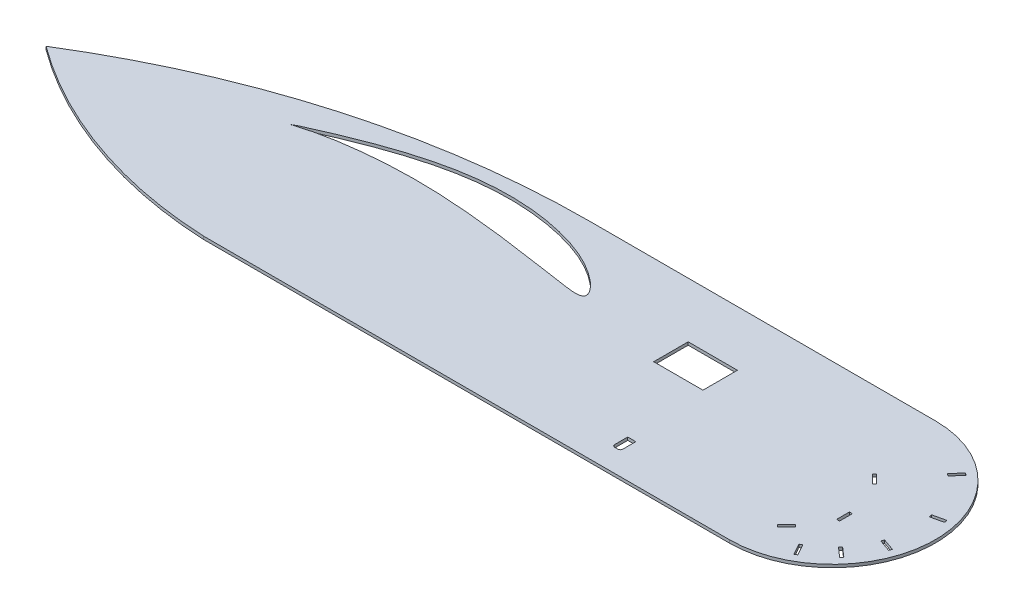
SolidWorks part; units mm, degrees
ref_plane "Front Plane" through (0, 0, 0) normal (0, 0, 1) x (1, 0, 0)
ref_plane "Top Plane" through (0, 0, 0) normal (0, 1, 0) x (1, 0, 0)
ref_plane "Right Plane" through (0, 0, 0) normal (1, 0, 0) x (0, 0, -1)
sketch "Sketch1" plane through (0, 0, 0) normal (0, 1, 0) x (1, 0, 0)
  line L0 (800, 104.5) -> (0, 104.5) construction
  line L1 (266.4083, 0) -> (800, 0)
  line L2 (0, 0) -> (0, 209) construction
  line L3 (449.0139, 209) -> (800, 209)
  line L7 (247.07, 156) -> (658.07, 156) construction
  arc A0 (800, 209) -> (800, 0) centre (800, 104.5) cw
  arc A2 (266.4083, 0) -> (19.4291, 86.8932) centre (286.1808, 450.645) cw
  arc A4 (19.4291, 86.8932) -> (449.0139, 209) centre (449.0139, -607.7159) cw
  point P1 (800, 202.4986)
  dimension "D1" = 800
  dimension "D2" = 53
extrude "Boss-Extrude1" add sketch "Sketch1" along normal blind 3
sketch "Sketch2" plane through (0, 0, 0) normal (0, -1, 0) x (1, 0, 0)
  line L0 (605.07, -153) -> (605.07, 81) construction
  line L1 (655.07, -153) -> (605.07, -153)
  line L2 (655.07, -153) -> (655.07, -118)
  line L3 (655.07, -118) -> (605.07, -118)
  line L4 (823.6893, -121.2328) -> (814.4969, -130.4252)
  line L5 (814.4969, -130.4252) -> (816.6182, -132.5465)
  line L6 (816.6182, -132.5465) -> (825.8106, -123.3541)
  line L7 (825.8106, -123.3541) -> (823.6893, -121.2328)
  line L8 (823.6893, -121.2328) -> (814.4969, -130.4252)
  line L9 (814.4969, -130.4252) -> (816.6182, -132.5465)
  line L10 (816.6182, -132.5465) -> (825.8106, -123.3541)
  line L11 (825.8106, -123.3541) -> (823.6893, -121.2328)
  line L12 (605.07, -153) -> (605.07, -118)
  line L20 (841.7076, -32.7369) -> (848.0358, -21.3811)
  line L21 (848.0358, -21.3811) -> (845.4152, -19.9208)
  line L22 (845.4152, -19.9208) -> (839.0871, -31.2766)
  line L23 (839.0871, -31.2766) -> (841.7076, -32.7369)
  line L24 (841.7076, -32.7369) -> (848.0358, -21.3811)
  line L25 (848.0358, -21.3811) -> (845.4152, -19.9208)
  line L26 (845.4152, -19.9208) -> (839.0871, -31.2766)
  line L27 (839.0871, -31.2766) -> (841.7076, -32.7369)
  line L28 (839.4566, -85.3169) -> (839.4566, -72.3169)
  line L29 (839.4566, -72.3169) -> (836.4566, -72.3169)
  line L30 (836.4566, -72.3169) -> (836.4566, -85.3169)
  line L31 (836.4566, -85.3169) -> (839.4566, -85.3169)
  line L32 (839.4566, -85.3169) -> (839.4566, -72.3169)
  line L33 (839.4566, -72.3169) -> (836.4566, -72.3169)
  line L34 (836.4566, -72.3169) -> (836.4566, -85.3169)
  line L35 (836.4566, -85.3169) -> (839.4566, -85.3169)
  line L37 (212.57, -142.2618) -> (212.57, -142.2948)
  line L38 (212.57, -142.2618) -> (212.57, -142.2948)
  line L40 (658.07, -25.4734) -> (658.07, -38.6734)
  line L41 (663.77, -22.9734) -> (660.57, -22.9734)
  line L42 (666.27, -38.6734) -> (666.27, -25.4734)
  line L43 (658.07, -38.6734) -> (666.27, -38.6734)
  line L44 (658.07, -25.4734) -> (658.07, -38.6734)
  line L45 (663.77, -22.9734) -> (660.57, -22.9734)
  line L46 (666.27, -38.6734) -> (666.27, -25.4734)
  line L47 (658.07, -38.6734) -> (666.27, -38.6734)
  line L188 (852.6149, -168.6961) -> (861.0358, -178.6) construction
  line L189 (861.0358, -178.6) -> (863.3214, -176.6567) construction
  line L190 (863.3214, -176.6567) -> (854.9004, -166.7528) construction
  line L191 (854.9004, -166.7528) -> (852.6149, -168.6961) construction
  line L192 (880.5688, -124.4531) -> (893.242, -127.3497) construction
  line L193 (893.242, -127.3497) -> (893.9105, -124.4251) construction
  line L194 (893.9105, -124.4251) -> (881.2373, -121.5286) construction
  line L195 (881.2373, -121.5286) -> (880.5688, -124.4531) construction
  line L196 (878.8444, -78.5572) -> (891.1176, -74.2715) construction
  line L197 (891.1176, -74.2715) -> (890.1286, -71.4393) construction
  line L198 (890.1286, -71.4393) -> (877.8554, -75.7249) construction
  line L199 (877.8554, -75.7249) -> (878.8444, -78.5572) construction
  line L200 (863.6104, -51.1786) -> (873.4206, -42.6486) construction
  line L201 (873.4206, -42.6486) -> (871.4522, -40.3847) construction
  line L202 (871.4522, -40.3847) -> (861.642, -48.9147) construction
  line L203 (861.642, -48.9147) -> (863.6104, -51.1786) construction
  line L204 (822.4089, -44.7346) -> (813.2165, -35.5422) construction
  line L205 (813.2165, -35.5422) -> (811.0952, -37.6635) construction
  line L206 (811.0952, -37.6635) -> (820.2876, -46.8559) construction
  line L207 (820.2876, -46.8559) -> (822.4089, -44.7346) construction
  line L208 (852.6149, -168.6961) -> (861.0358, -178.6)
  line L209 (861.0358, -178.6) -> (863.3214, -176.6567)
  line L210 (863.3214, -176.6567) -> (854.9004, -166.7528)
  line L211 (854.9004, -166.7528) -> (852.6149, -168.6961)
  line L212 (880.5688, -124.4531) -> (893.242, -127.3497)
  line L213 (893.242, -127.3497) -> (893.9105, -124.4251)
  line L214 (893.9105, -124.4251) -> (881.2373, -121.5286)
  line L215 (881.2373, -121.5286) -> (880.5688, -124.4531)
  line L216 (878.8444, -78.5572) -> (891.1176, -74.2715)
  line L217 (891.1176, -74.2715) -> (890.1286, -71.4393)
  line L218 (890.1286, -71.4393) -> (877.8554, -75.7249)
  line L219 (877.8554, -75.7249) -> (878.8444, -78.5572)
  line L220 (863.6104, -51.1786) -> (873.4206, -42.6486)
  line L221 (873.4206, -42.6486) -> (871.4522, -40.3847)
  line L222 (871.4522, -40.3847) -> (861.642, -48.9147)
  line L223 (861.642, -48.9147) -> (863.6104, -51.1786)
  line L224 (822.4089, -44.7346) -> (813.2165, -35.5422)
  line L225 (813.2165, -35.5422) -> (811.0952, -37.6635)
  line L226 (811.0952, -37.6635) -> (820.2876, -46.8559)
  line L227 (820.2876, -46.8559) -> (822.4089, -44.7346)
  arc A2 (660.57, -22.9734) -> (658.07, -25.4734) centre (660.57, -25.4734) ccw
  arc A3 (666.27, -25.4734) -> (663.77, -22.9734) centre (663.77, -25.4734) ccw
  arc A4 (660.57, -22.9734) -> (658.07, -25.4734) centre (660.57, -25.4734) ccw
  arc A5 (666.27, -25.4734) -> (663.77, -22.9734) centre (663.77, -25.4734) ccw
  spline S1 degree 3 poles (-935.9633, -1778.8288) (190.5889, -95.3438) (194.6064, -131.763) (215.6642, -144.2206) (218.7234, -145.7779) (222.7838, -147.5804) (227.7591, -149.7808) (233.6732, -152.3729) (243.3346, -156.474) (254.0716, -160.9286) (265.8113, -165.5514) (275.5598, -169.1926) (285.8203, -172.7897) (300.2132, -177.4429) (315.0475, -181.6144) (330.2168, -185.0782) (341.7168, -187.2628) (353.2384, -188.9705) (364.7498, -190.1898) (376.2222, -190.8893) (387.6115, -191.0869) (398.8538, -190.7647) (413.4214, -189.6963) (427.5808, -187.7) (441.1954, -184.8275) (450.8219, -182.3197) (459.9489, -179.4697) (468.5117, -176.2876) (476.4536, -172.8247) (483.7151, -169.1289) (490.2481, -165.2848) (496.0197, -161.4069) (500.998, -157.5857) (505.1476, -153.8841) (508.4473, -150.3827) (510.8522, -147.1808) (512.2305, -144.519) (512.6724, -142.438) (512.366, -140.694) (510.8363, -139.2679) (508.3008, -138.6046) (504.9907, -138.3969) (500.8451, -138.6329) (495.8864, -139.207) (490.1274, -140.0338) (483.6007, -141.0142) (476.346, -142.082) (468.4189, -143.2709) (459.8696, -144.553) (447.4042, -146.414) (434.3028, -148.292) (413.2306, -151.0803) (394.9165, -153.1705) (372.4131, -155.1852) (353.2786, -156.4974) (334.1039, -157.1205) (318.8375, -157.1193) (307.5693, -156.8631) (296.5448, -156.3424) (285.8536, -155.5986) (275.5863, -154.6546) (265.8296, -153.5569) (256.6735, -152.3128) (248.205, -150.9585) (240.5101, -149.5233) (233.6661, -148.0641) (227.7356, -146.6296) (222.7715, -145.2056) (218.7746, -143.9126) (215.7248, -142.9952) (193.3721, -137.343) (166.6151, -157.487) (567.9657, 1824.9991) knots -0.10608 -0.10608 -0.10608 -0.10608 0.001413 0.005226 0.010781 0.017816 0.026461 0.036791 0.048686 0.076639 0.092363 0.109003 0.126387 0.144339 0.181313 0.200023 0.218713 0.237261 0.255692 0.274037 0.292193 0.310133 0.327788 0.362002 0.378421 0.394287 0.409543 0.424114 0.437938 0.450942 0.463044 0.474154 0.484165 0.493024 0.500713 0.507126 0.51213 0.514904 0.517171 0.520262 0.524245 0.529498 0.536092 0.544061 0.553363 0.563905 0.575615 0.58842 0.602227 0.616944 0.648676 0.665501 0.718564 0.736789 0.773513 0.810245 0.828489 0.846493 0.864125 0.881249 0.897725 0.913415 0.928184 0.941897 0.954411 0.965603 0.97535 0.983576 0.990285 0.995433 0.9988 1.100441 1.100441 1.100441 1.100441 only from (212.57, -142.2948) to (212.57, -142.2618)
  spline S2 degree 3 poles (212.57, -142.2948) (212.8151, -142.4601) (213.7215, -143.0713) (215.6642, -144.2206) (218.7234, -145.7779) (222.7838, -147.5804) (227.7591, -149.7808) (233.6732, -152.3729) (243.3346, -156.474) (254.0716, -160.9286) (265.8113, -165.5514) (275.5598, -169.1926) (285.8203, -172.7897) (300.2132, -177.4429) (315.0475, -181.6144) (330.2168, -185.0782) (341.7168, -187.2628) (353.2384, -188.9705) (364.7498, -190.1898) (376.2222, -190.8893) (387.6115, -191.0869) (398.8538, -190.7647) (413.4214, -189.6963) (427.5808, -187.7) (441.1954, -184.8275) (450.8219, -182.3197) (459.9489, -179.4697) (468.5117, -176.2876) (476.4536, -172.8247) (483.7151, -169.1289) (490.2481, -165.2848) (496.0197, -161.4069) (500.998, -157.5857) (505.1476, -153.8841) (508.4473, -150.3827) (510.8522, -147.1808) (512.2305, -144.519) (512.6724, -142.438) (512.366, -140.694) (510.8363, -139.2679) (508.3008, -138.6046) (504.9907, -138.3969) (500.8451, -138.6329) (495.8864, -139.207) (490.1274, -140.0338) (483.6007, -141.0142) (476.346, -142.082) (468.4189, -143.2709) (459.8696, -144.553) (447.4042, -146.414) (434.3028, -148.292) (413.2306, -151.0803) (394.9165, -153.1705) (372.4131, -155.1852) (353.2786, -156.4974) (334.1039, -157.1205) (318.8375, -157.1193) (307.5693, -156.8631) (296.5448, -156.3424) (285.8536, -155.5986) (275.5863, -154.6546) (265.8296, -153.5569) (256.6735, -152.3128) (248.205, -150.9585) (240.5101, -149.5233) (233.6661, -148.0641) (227.7356, -146.6296) (222.7715, -145.2056) (218.7746, -143.9126) (215.7248, -142.9952) (213.7534, -142.4967) (212.8162, -142.3107) (212.57, -142.2618) knots 0 0 0 0 0.001413 0.005226 0.010781 0.017816 0.026461 0.036791 0.048686 0.076639 0.092363 0.109003 0.126387 0.144339 0.181313 0.200023 0.218713 0.237261 0.255692 0.274037 0.292193 0.310133 0.327788 0.362002 0.378421 0.394287 0.409543 0.424114 0.437938 0.450942 0.463044 0.474154 0.484165 0.493024 0.500713 0.507126 0.51213 0.514904 0.517171 0.520262 0.524245 0.529498 0.536092 0.544061 0.553363 0.563905 0.575615 0.58842 0.602227 0.616944 0.648676 0.665501 0.718564 0.736789 0.773513 0.810245 0.828489 0.846493 0.864125 0.881249 0.897725 0.913415 0.928184 0.941897 0.954411 0.965603 0.97535 0.983576 0.990285 0.995433 0.9988 1 1 1 1
  dimension "D6" = 35
  dimension "D1" = 0
  dimension "D2" = 0
  dimension "D3" = 0
  dimension "D4" = 0
  dimension "D5" = 0
extrude "Cut-Extrude1" cut sketch "Sketch2" against normal through all
